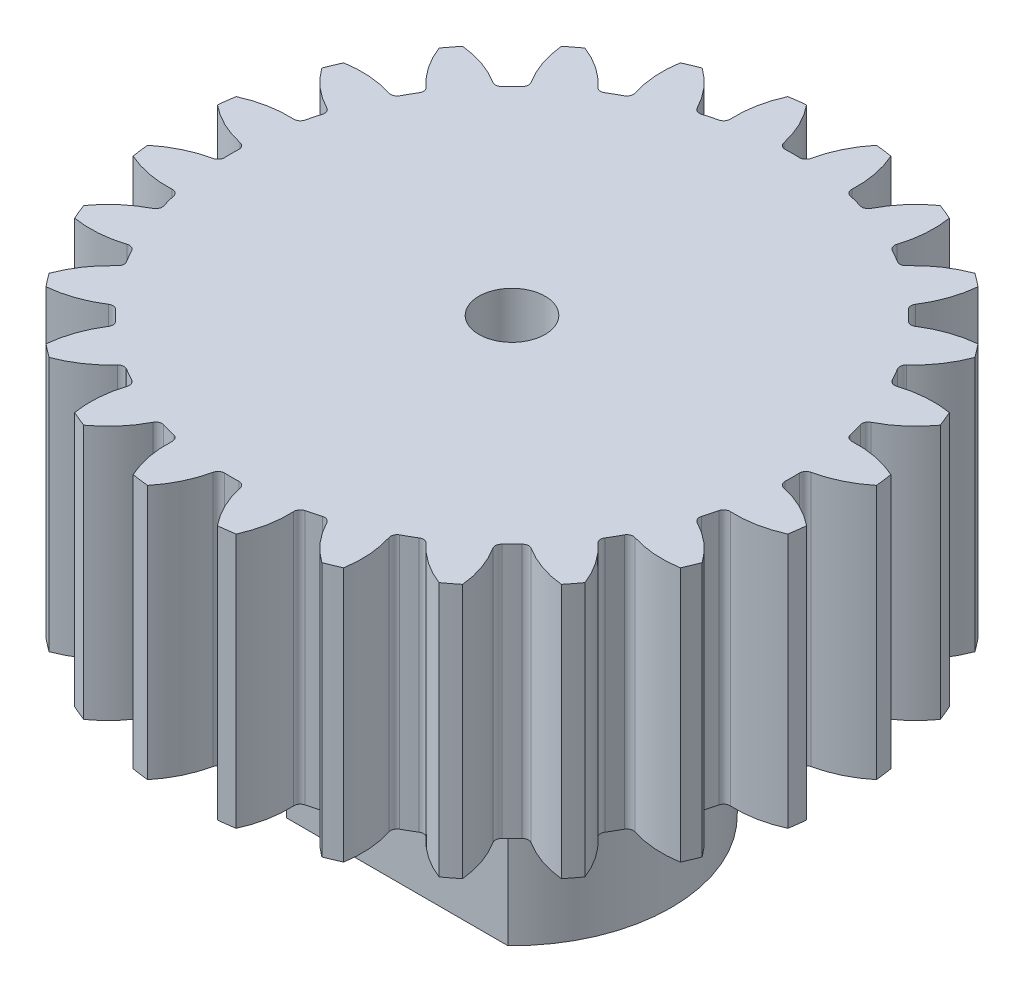
SolidWorks part; units mm, degrees
material "聚脂树脂"
ref_plane "前视基准面" through (0, 0, 0) normal (0, 0, 1) x (1, 0, 0)
ref_plane "上视基准面" through (0, 0, 0) normal (0, 1, 0) x (1, 0, 0)
ref_plane "右视基准面" through (0, 0, 0) normal (1, 0, 0) x (0, 0, -1)
other "Configuration Table"
sketch "草图1" plane through (0, 0, 0) normal (0, 1, 0) x (1, 0, 0)
  circle A0 centre (0, 0) radius 26
  dimension "D1" = 52
extrude "凸台-拉伸1" add sketch "草图1" along normal blind 20
sketch "草图2" plane through (0, 0, 0) normal (0, 1, 0) x (1, 0, 0)
  circle A0 centre (0, 0) radius 12.5
  dimension "D1" = 25
extrude "凸台-拉伸2" add sketch "草图2" against normal blind 14
sketch "草图4" plane through (0, 0, 0) normal (0, 1, 0) x (1, 0, 0)
  line L0 (0, 56.0311) -> (0, -31.5538) construction
  line L1 (0, 0) -> (3.6369, 55.4876) construction
  line L2 (1.5697, 23.9486) -> (26.6905, 22.3021) construction
  line L3 (1.5697, 23.9486) -> (25.0859, 13.6012) construction
  line L4 (9.083, 20.6427) -> (0, 0) construction
  circle A0 centre (0, 0) radius 24 construction
  arc A2 (2.7418, 25.855) -> (1.0619, 22.3865) centre (9.083, 20.6427) ccw
  arc A8 (2.7418, 25.855) -> (-2.7418, 25.855) centre (0, 0) ccw
  circle A9 centre (0, 0) radius 26 construction
  arc A15 (0.5605, 21.9929) -> (-0.5605, 21.9929) centre (0, 0) ccw
  arc A16 (1.0619, 22.3865) -> (0.5605, 21.9929) centre (0.5733, 22.4927) cw
  arc A17 (-1.0619, 22.3865) -> (-0.5605, 21.9929) centre (-0.5733, 22.4927) ccw
  arc A18 (-2.7418, 25.855) -> (-1.0619, 22.3865) centre (-9.083, 20.6427) cw
  dimension "D1" = 48
  dimension "D4" = 22
  dimension "D5" = 0.5
  dimension "D2" = 3.75
  dimension "D3" = 20
extrude "切除-拉伸1" cut sketch "草图4" along normal up to next
pattern_circular "阵列(圆周)1" count 24 over 360 about axis through (0, 20, 0) along (0, 1, 0) of "切除-拉伸1"
sketch "草图6" plane through (0, 0, 0) normal (0, 1, 0) x (1, 0, 0)
  circle A0 centre (0, 0) radius 24 construction
  dimension "D1" = 48
sketch "草图8" plane through (0, 0, 0) normal (0, 0, 1) x (1, 0, 0)
  line L0 (-12.5, -14) -> (12.5, -14) construction
  line L1 (-12.5, -14) -> (12.5, -14)
  line L2 (-12.5, -14) -> (-12.5, 0)
  line L3 (-12.5, 0) -> (12.5, 0)
  line L4 (12.5, -14) -> (12.5, 0)
  line L5 (24, 0) -> (-24, 0) construction
  line L6 (0, -17.9573) -> (0, 22.5638) construction
  dimension "D1" = 25
sketch "草图7" plane through (0, 0, 0) normal (0, 0, 1) x (1, 0, 0)
  line L0 (0, 37.4487) -> (0, -32.2732) construction
  line L1 (-12.5, -14) -> (12.5, -14) construction
  circle A0 centre (-4.5, -7) radius 2.15
  circle A1 centre (4.5, -7) radius 2.15
  dimension "D1" = 4.3
  dimension "D2" = 9
  dimension "D3" = 7
extrude "切除-拉伸4" cut sketch "草图7" against normal through all both and the other way through all
sketch "草图5" plane through (0, 0, 0) normal (0, 1, 0) x (1, 0, 0)
  circle A0 centre (0, 0) radius 2.6
  dimension "D1" = 5.2
extrude "切除-拉伸2" cut sketch "草图5" against normal through all both and the other way through all
extrude "切除-拉伸5" cut sketch "草图8" along normal blind 3.5 from offset 12.5 offset against normal yes
extrude "切除-拉伸6" cut sketch "草图8<2>" against normal blind 3.5 from offset 12.5
sketch "草图8<2>" plane through (0, 0, 0) normal (0, 0, 1) x (1, 0, 0) same geometry as "草图8"
